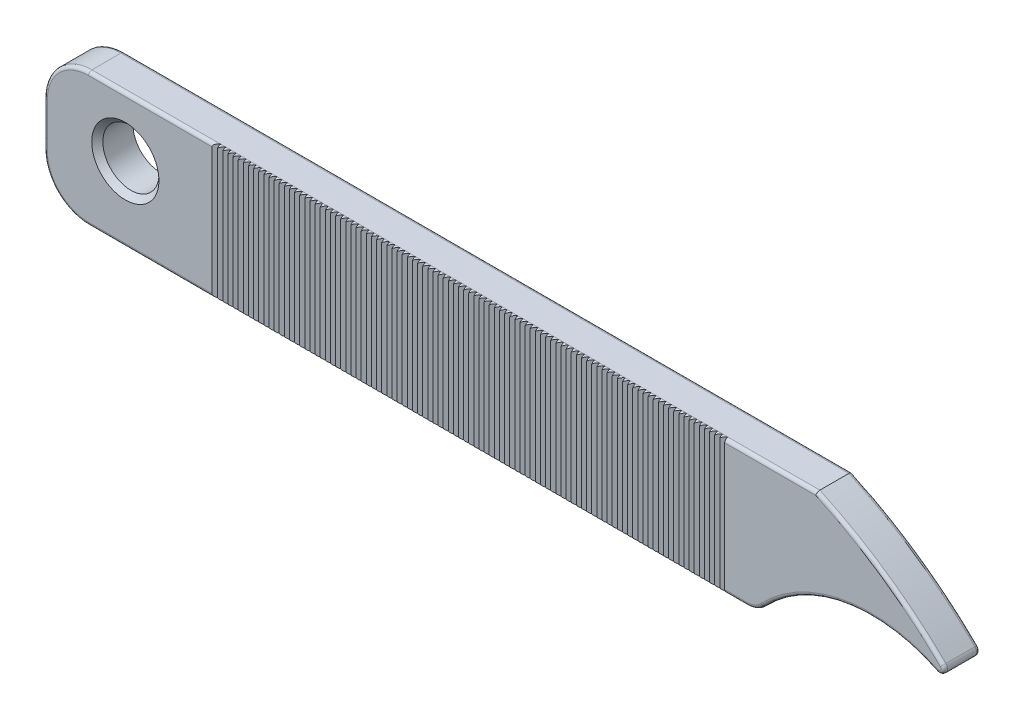
SolidWorks part; units mm, degrees
ref_plane "Płaszczyzna przednia" through (0, 0, 0) normal (0, 0, 1) x (1, 0, 0)
ref_plane "Płaszczyzna górna" through (0, 0, 0) normal (0, 1, 0) x (1, 0, 0)
ref_plane "Płaszczyzna prawa" through (0, 0, 0) normal (1, 0, 0) x (0, 0, -1)
sketch "Sketch1" plane through (0, 0, 0) normal (0, 0, 1) x (1, 0, 0)
  line L0 (-1.5855, 0) -> (-33.5855, 0)
  line L1 (-33.5855, 0) -> (-33.5855, 6)
  line L2 (-33.5855, 6) -> (1.0944, 6)
  arc A2 (1.0944, 6) -> (8.4145, 0.25) centre (-7.2608, -12.1712) cw
  arc A3 (-1.5855, 0) -> (8.4145, 0.25) centre (3.5254, -4.3096) cw
  dimension "D5" = 20
  dimension "D1" = 6
  dimension "D2" = 42
  dimension "D3" = 32
  dimension "D4" = 5.75
extrude "Boss-Extrude2" add sketch "Sketch1" along normal blind 1.6
fillet "Fillet1" radius 1 1 edges at (-1.5855, 0, 0.8)
fillet "Fillet2" radius 0.25 1 edges at (8.4145, 0.25, 0.8)
fillet "Fillet3" radius 2 2 edges at (-33.5855, 0, 0.8) (-33.5855, 6, 0.8)
fillet "Fillet4" radius 0.15 18 edges at (4.0949, 4.2924, 0) (6.7858, 1.7714, 0) (2.3558, 2.2726, 0) (-1.6378, 0.0805, 0) (-16.8082, 0, 0) (-32.9997, 0.5858, 0) (-33.5855, 3, 0) (-32.9997, 5.4142, 0) (4.0949, 4.2924, 1.6) (6.7858, 1.7714, 1.6) (2.3558, 2.2726, 1.6) (-1.6378, 0.0805, 1.6) (-16.8082, 0, 1.6) (-32.9997, 0.5858, 1.6) (-33.5855, 3, 1.6) (-32.9997, 5.4142, 1.6) (-15.2456, 6, 0) (-15.2456, 6, 1.6)
sketch "Sketch2" plane through (0, 0, 1.6) normal (0, 0, 1) x (1, 0, 0)
  line L0 (-33.4355, 4) -> (-33.4355, 2) construction
  line L1 (-31.5855, 0.15) -> (-2.0309, 0.15) construction
  circle A0 centre (-29.9355, 3.35) radius 1.259
  dimension "D1" = 2.5179
  dimension "D2" = 3.5
  dimension "D3" = 3.2
extrude "Cut-Extrude1" cut sketch "Sketch2" against normal through all contours A0
chamfer "Chamfer1" distance 0.25 angle 45 1 edges at (-28.6765, 3.35, 1.6)
sketch "Sketch3" plane through (0, 0, 0) normal (0, -1, 0) x (1, 0, 0)
  line L0 (-3.2809, 1.6) -> (-3.0309, 1.45)
  line L1 (-31.5855, 1.6) -> (-2.0309, 1.6) construction
  line L2 (-2.0309, 1.45) -> (-31.5855, 1.45) construction
  line L3 (-3.0309, 1.45) -> (-3.0309, 1.6)
  line L4 (-2.0309, 1.6) -> (-2.0309, 1.45) construction
  dimension "D1" = 0.25
  dimension "D2" = 1
extrude "Cut-Extrude2" cut sketch "Sketch3" against normal through all and the other way through all
pattern_linear "LPattern1" count 100 spacing 0.23 along (-1, 0, 0) of "Cut-Extrude2"
